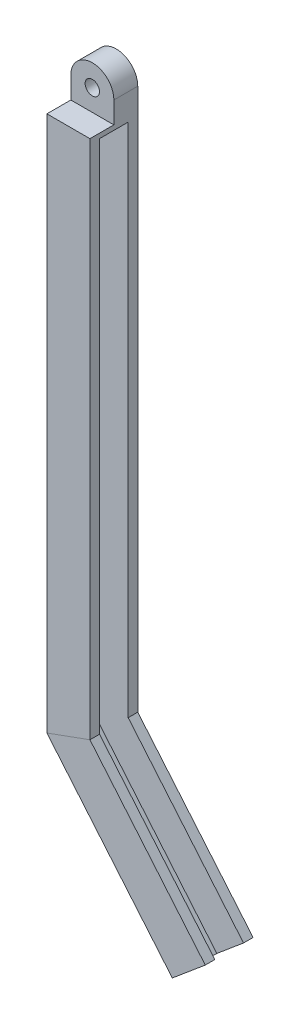
SolidWorks part; units mm, degrees
ref_plane "前视基准面" through (0, 0, 0) normal (0, 0, 1) x (1, 0, 0)
ref_plane "上视基准面" through (0, 0, 0) normal (0, 1, 0) x (1, 0, 0)
ref_plane "右视基准面" through (0, 0, 0) normal (1, 0, 0) x (0, 0, -1)
sketch "草图4" plane through (0, 0, 0) normal (0, 1, 0) x (1, 0, 0)
  line L0 (-24.3, 1.0429) -> (-15.3, 1.0429)
  line L1 (-15.3, 1.0429) -> (-15.3, -8.9571)
  line L2 (-15.3, -8.9571) -> (-24.3, -8.9571)
  line L3 (-24.3, -8.9571) -> (-24.3, 1.0429)
  line L4 (-24.3, 1.0429) -> (-15.3, -8.9571) construction
  line L5 (-15.3, 1.0429) -> (-24.3, -8.9571) construction
  point P3 (-19.8, -3.9571)
  dimension "D1" = 9
  dimension "D2" = 10
extrude "凸台-拉伸2" add sketch "草图4" along normal blind 10
ref_plane "镜腿扫描轨迹基准面" through (0, 0, 3.9571) normal (0, 0, 1) x (1, 0, 0)
sketch "草图5" plane through (0, 0, 3.9571) normal (0, 0, 1) x (1, 0, 0)
  line L0 (-19.8, 0) -> (-19.8, -110)
  line L1 (-24.3, 0) -> (-15.3, 0) construction
  line L2 (-19.8, -110) -> (5.373, -140)
  dimension "D1" = 110
  dimension "D2" = 30
  dimension "D3" = 140
sketch "草图6" plane through (0, 0, 8.9571) normal (0, 0, 1) x (1, 0, 0)
  line L0 (-24.3, 10) -> (-24.3, 5)
  line L1 (-24.3, 10) -> (-24.3, 0) construction
  line L2 (-24.3, 10) -> (-15.3, 10)
  line L3 (-15.3, 10) -> (-15.3, 5)
  line L4 (-15.3, 10) -> (-15.3, 0) construction
  arc A0 (-24.3, 5) -> (-15.3, 5) centre (-19.8, 5) cw
  dimension "D1" = 5
  dimension "D2" = 5
extrude "切除-拉伸1" cut sketch "草图6" against normal blind 10
sweep "扫描2" add profiles "草图4<2>" path "草图5"
sketch "草图4<2>" plane through (0, 0, 0) normal (0, 1, 0) x (1, 0, 0) same geometry as "草图4"
ref_plane "connection口生成草图基准面" through (0, 0, 3.9571) normal (0, 0, 1) x (1, 0, 0)
sketch "草图7" plane through (0, 0, 3.9571) normal (0, 0, 1) x (1, 0, 0)
  line L0 (-24.3, 5) -> (-24.3, 0.5)
  line L1 (-24.3, 5) -> (-24.3, -111.6379) construction
  line L2 (-24.3, 0.5) -> (-15.3, 0.5)
  line L3 (-15.3, 5) -> (-15.3, -108.3621) construction
  line L4 (-15.3, 0.5) -> (-15.3, 5)
  arc A0 (-24.3, 5) -> (-15.3, 5) centre (-19.8, 5) cw
  dimension "D1" = 4.5
extrude "切除-拉伸2" cut sketch "草图7" along normal blind 10
sketch "草图8" plane through (0, 0, 3.9571) normal (0, 0, 1) x (1, 0, 0)
  line L3 (-15.3, 0.5) -> (-15.3, 5)
  line L4 (-24.3, 0.5) -> (-15.3, 0.5)
  line L5 (-24.3, 5) -> (-24.3, 0.5)
  line L6 (-15.3, 0.5) -> (-15.3, 5)
  line L7 (-24.3, 0.5) -> (-15.3, 0.5)
  line L8 (-24.3, 5) -> (-24.3, 0.5)
  circle A0 centre (-19.8, 5) radius 1.5
  arc A1 (-15.3, 5) -> (-24.3, 5) centre (-19.8, 5) ccw
  arc A2 (-15.3, 5) -> (-24.3, 5) centre (-19.8, 5) ccw
  dimension "D2" = 3
  dimension "D1" = 0
extrude "切除-拉伸3" cut sketch "草图8" against normal blind 10 contours A0
ref_plane "基准面3" through (0, -0.5, 0) normal (0, 1, 0) x (1, 0, 0)
sketch "草图9" plane through (0, -0.5, 0) normal (0, 1, 0) x (1, 0, 0)
  line L16 (-15.3, -0.9571) -> (-15.3, -6.9571)
  line L17 (-15.3, 1.0429) -> (-15.3, -8.9571) construction
  line L18 (-15.3, -8.9571) -> (-15.3, -3.9571) construction
  line L19 (-15.3, -6.9571) -> (-22.59, -6.9571)
  line L20 (-22.59, -6.9571) -> (-22.59, -0.9571)
  line L21 (-22.59, -0.9571) -> (-15.3, -0.9571)
  line L22 (-15.3, 1.0429) -> (-24.3, 1.0429) construction
  point P10 (-19.8, -2.6021)
  dimension "D1" = 6
  dimension "D2" = 2
  dimension "D3" = 7.29
ref_plane "基准面6" through (0, 0, 2.6021) normal (0, 0, 1) x (1, 0, 0)
extrude "切除-拉伸5" cut sketch "草图9" against normal blind 110
sketch "草图13" plane through (71.1565, -84.8011, 0) normal (0.6428, -0.766, 0) x (0.766, 0.6428, 0)
  line L0 (-81.3743, 6.9571) -> (-81.3743, 0.9571)
  line L1 (-81.3743, 0.9571) -> (-88.6643, 0.9571)
  line L2 (-88.333, 0.9571) -> (-17.6263, 0.9571) construction
  line L3 (-88.6643, 0.9571) -> (-88.6643, 6.9571)
  line L4 (-88.333, 6.9571) -> (-17.6263, 6.9571) construction
  line L5 (-88.6643, 6.9571) -> (-81.3743, 6.9571)
  dimension "D1" = 7.29
extrude "切除-拉伸6" cut sketch "草图13" against normal blind 40
